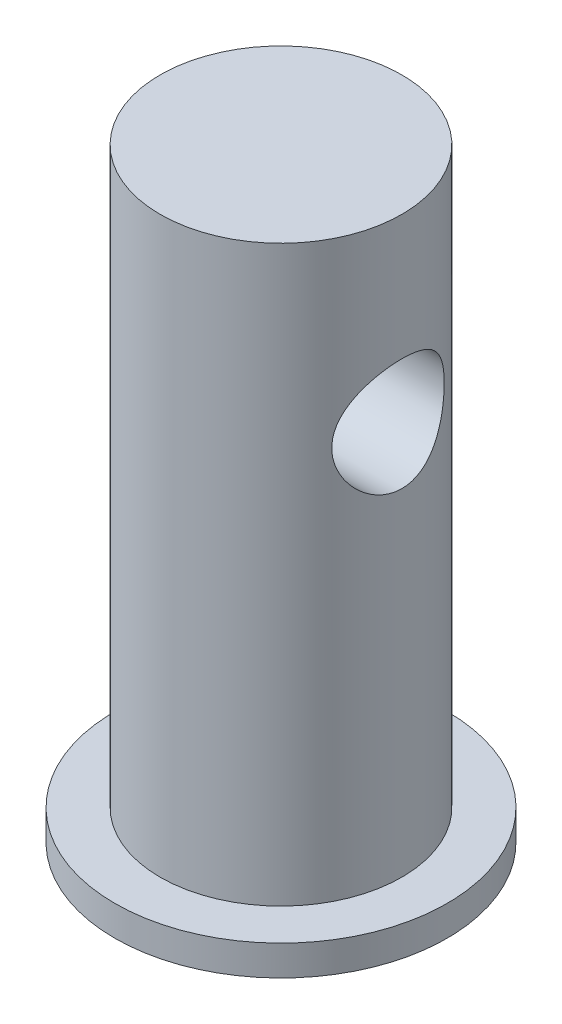
SolidWorks part; units mm, degrees
ref_plane "Front Plane" through (0, 0, 0) normal (0, 0, 1) x (1, 0, 0)
ref_plane "Top Plane" through (0, 0, 0) normal (0, 1, 0) x (1, 0, 0)
ref_plane "Right Plane" through (0, 0, 0) normal (1, 0, 0) x (0, 0, -1)
sketch "Sketch1" plane through (0, 0, 0) normal (0, 1, 0) x (1, 0, 0)
  circle A0 centre (0, 0) radius 4
  circle A1 centre (0, 0) radius 5.5
  dimension "D1" = 8
  dimension "D2" = 11
extrude "Boss-Extrude1" add sketch "Sketch1" along normal blind 1
extrude "Boss-Extrude2" add sketch "Sketch1<2>" along normal blind 20 contours A0 region at (0, 0, 0)
sketch "Sketch1<2>" plane through (0, 0, 0) normal (0, 1, 0) x (1, 0, 0) same geometry as "Sketch1"
ref_plane "Plane1" through (4, 0, 0) normal (1, 0, 0) x (0, 0, -1)
sketch "Sketch2" plane through (4, 0, 0) normal (1, 0, 0) x (0, 0, -1)
  line L0 (5.5, 1) -> (-5.5, 1) construction
  circle A0 centre (0, 14) radius 1.8612
  dimension "D1" = 13
extrude "Cut-Extrude1" cut sketch "Sketch2" against normal blind 12
